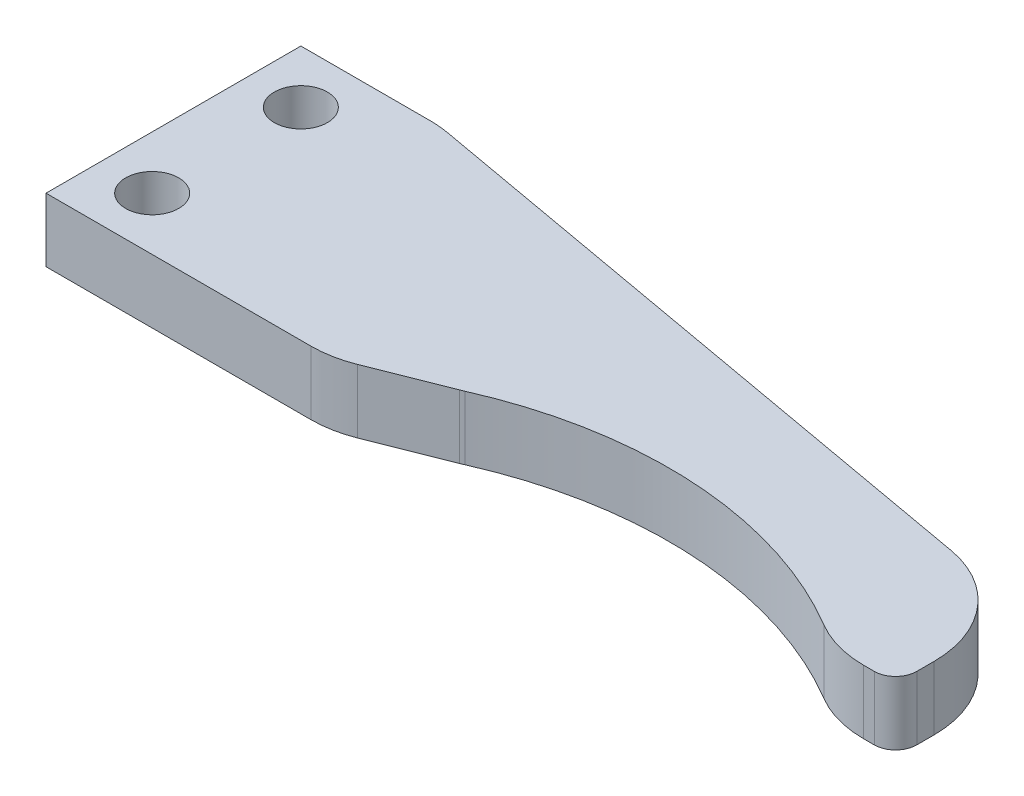
SolidWorks part; units mm, degrees
ref_plane "Front Plane" through (0, 0, 0) normal (0, 0, 1) x (1, 0, 0)
ref_plane "Top Plane" through (0, 0, 0) normal (0, 1, 0) x (1, 0, 0)
ref_plane "Right Plane" through (0, 0, 0) normal (1, 0, 0) x (0, 0, -1)
sketch "Sketch1" plane through (0, 0, 0) normal (0, 1, 0) x (1, 0, 0)
  line L1 (20, -6) -> (-20, -6)
  line L2 (20, -6) -> (20, 6)
  line L3 (20, 6) -> (-20, 6)
  line L4 (-20, -6) -> (-20, 6)
  line L5 (20, -6) -> (-20, 6) construction
  line L6 (20, 6) -> (-20, -6) construction
  point P0 (0, 0)
  dimension "D1" = 12
  dimension "D2" = 40
extrude "Boss-Extrude1" add sketch "Sketch1" along normal blind 3
sketch "Sketch3" plane through (0, 3, 0) normal (0, 1, 0) x (1, 0, 0)
  line L0 (-20, 6) -> (-20, -6) construction
  line L1 (20, 6) -> (-20, 6) construction
  line L2 (-20, -6) -> (20, -6) construction
  circle A0 centre (-17.5, 3.5) radius 1.25
  circle A1 centre (-17.5, -3.5) radius 1.25
  dimension "D1" = 2.5
  dimension "D3" = 2.5
  dimension "D4" = 2.5
  dimension "D5" = 2.5
  dimension "D2" = 2.5
  dimension "D6" = 2.5
extrude "Cut-Extrude2" cut sketch "Sketch3" against normal through all
sketch "Sketch5" plane through (0, 3, 0) normal (0, 1, 0) x (1, 0, 0)
  line L0 (-13.4582, 6) -> (20, 0)
  line L2 (20, 6) -> (-20, 6) construction
  line L3 (20, -6) -> (20, 6) construction
  line L4 (20, 0) -> (20, -6)
  line L5 (20, -6) -> (17.0301, -6)
  line L6 (-20, -6) -> (20, -6) construction
  line L7 (-2.1446, -4.2501) -> (-6.5697, -6)
  line L8 (-6.5697, -6) -> (-13.4582, -6)
  line L9 (-13.4582, -6) -> (-13.4582, -10.2372)
  line L10 (-13.4582, -10.2372) -> (26.0235, -9.7269)
  line L11 (26.0235, -9.7269) -> (26.0235, 8.4773)
  line L12 (26.0235, 8.4773) -> (-13.4582, 8.4773)
  line L13 (-13.4582, 8.4773) -> (-13.4582, 6)
  arc A0 (17.0301, -6) -> (-2.1446, -4.2501) centre (5.8843, -22.2017) ccw
extrude "Cut-Extrude3" cut sketch "Sketch5" against normal blind 10
fillet "Fillet2" radius 5 3 edges at (17.0301, 1.5, 6) (-2.1446, 1.5, 4.2501) (-6.5697, 1.5, 6)
fillet "Fillet3" radius 1 1 edges at (20, 1.5, 6)
fillet "Fillet4" radius 5 1 edges at (20, 1.5, 0)
fillet "Fillet5" radius 5 1 edges at (-13.4582, 1.5, -6)
